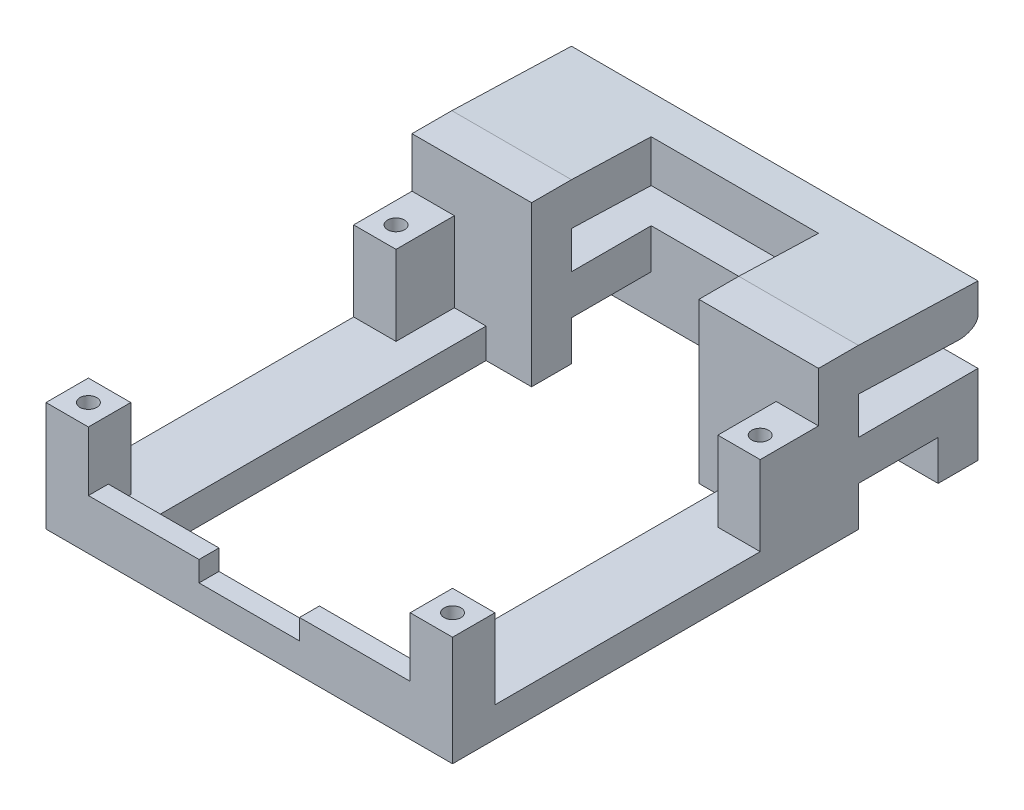
SolidWorks part; units mm, degrees
ref_plane "Front Plane" through (0, 0, 0) normal (0, 0, 1) x (1, 0, 0)
ref_plane "Top Plane" through (0, 0, 0) normal (0, 1, 0) x (1, 0, 0)
ref_plane "Right Plane" through (0, 0, 0) normal (1, 0, 0) x (0, 0, -1)
sketch "Sketch1" plane through (0, 0, 0) normal (0, 1, 0) x (1, 0, 0)
  line L0 (-25.625, 13.905) -> (-25.625, 16.445)
  line L1 (32.375, 41.845) -> (-32.375, 41.845)
  line L2 (32.375, 41.845) -> (32.375, -41.845)
  line L3 (32.375, -41.845) -> (-32.375, -41.845)
  line L4 (-32.375, 41.845) -> (-32.375, -41.845)
  line L5 (32.375, 41.845) -> (-32.375, -41.845) construction
  line L6 (32.375, -41.845) -> (-32.375, 41.845) construction
  line L13 (-32.375, 13.905) -> (-25.625, 13.905)
  line L14 (-32.375, 13.905) -> (-32.375, 7.155)
  line L15 (-32.375, 7.155) -> (-25.625, 7.155)
  line L16 (-25.625, 13.905) -> (-25.625, 7.155)
  line L17 (-32.375, 13.905) -> (-25.625, 7.155) construction
  line L18 (-32.375, 7.155) -> (-25.625, 13.905) construction
  line L19 (25.625, 7.155) -> (32.375, 7.155)
  line L20 (25.625, 7.155) -> (25.625, 13.905)
  line L21 (25.625, 13.905) -> (32.375, 13.905)
  line L22 (32.375, 7.155) -> (32.375, 13.905)
  line L23 (25.625, 7.155) -> (32.375, 13.905) construction
  line L24 (25.625, 13.905) -> (32.375, 7.155) construction
  line L25 (25.625, -35.095) -> (32.375, -35.095)
  line L26 (25.625, -35.095) -> (25.625, -41.845)
  line L27 (25.625, -41.845) -> (32.375, -41.845)
  line L28 (32.375, -35.095) -> (32.375, -41.845)
  line L29 (25.625, -35.095) -> (32.375, -41.845) construction
  line L30 (25.625, -41.845) -> (32.375, -35.095) construction
  line L31 (-25.625, -35.095) -> (-32.375, -35.095)
  line L32 (-25.625, -35.095) -> (-25.625, -41.845)
  line L33 (-25.625, -41.845) -> (-32.375, -41.845)
  line L34 (-32.375, -35.095) -> (-32.375, -41.845)
  line L35 (-25.625, -35.095) -> (-32.375, -41.845) construction
  line L36 (-25.625, -41.845) -> (-32.375, -35.095) construction
  line L47 (-32.375, -41.845) -> (32.375, -41.845)
  line L56 (-25.625, 16.445) -> (-32.375, 16.445)
  line L58 (25.625, 13.905) -> (25.625, 16.445)
  line L59 (25.625, 16.445) -> (32.375, 16.445)
  circle A0 centre (-29, 10.53) radius 1.35
  circle A1 centre (29, 10.53) radius 1.35
  circle A2 centre (-29, -38.47) radius 1.35
  circle A3 centre (29, -38.47) radius 1.35
  point P0 (0, 0)
  point P27 (0, 0)
  dimension "D1" = 2.7
  dimension "D2" = 58
  dimension "D3" = 49
  dimension "D4" = 25.4
  dimension "D5" = 6.75
  dimension "D6" = 2.54
extrude "Boss-Extrude1" add sketch "Sketch1" along normal blind 25.4 contours L31 L32 L3 L26 L25 L2 L19 L20 L21 L1 L4 L13 L16 L15 | L32 L31 L4 L3 A2 | L25 L26 L3 L2 A3 | L21 L20 L19 L2 A1 | L16 L13 L4 L15 A0 | L0 L56 L4 L13 | L59 L58 L21 L2 region at (-29, 0, -15.175) region at (-25.7205, 0, -10.53) region at (0, 0, -0.3894) region at (-29, 0, 35.1905) region at (29, 0, -15.175) region at (32.2795, 0, -10.53) region at (25.7205, 0, 38.47)
sketch "Sketch3" plane through (32.375, 0, 0) normal (1, 0, 0) x (0, 0, -1)
  line L0 (41.845, 18.034) -> (22.795, 18.669)
  line L1 (41.845, 25.4) -> (41.845, 0) construction
  line L2 (22.795, 18.669) -> (22.795, 12.7)
  line L3 (22.795, 12.7) -> (41.845, 12.7)
  line L4 (41.845, 12.7) -> (41.845, 18.034)
  line L5 (41.845, 0) -> (-41.845, 0) construction
  line L6 (41.845, 25.4) -> (22.795, 25.4)
  line L7 (41.845, 25.4) -> (-41.845, 25.4) construction
  line L8 (22.795, 25.4) -> (41.845, 24.765)
  line L9 (41.845, 25.4) -> (41.845, 0) construction
  line L10 (41.845, 24.765) -> (41.845, 25.4)
  point P16 (22.795, 25.4)
  dimension "D1" = 5.969
  dimension "D2" = 5.334
  dimension "D3" = 19.05
  dimension "D4" = 12.7
extrude "Cut-Extrude1" cut sketch "Sketch3" against normal through all
sketch "Sketch5" plane through (32.375, 0, 0) normal (1, 0, 0) x (0, 0, -1)
  line L0 (16.445, 25.4) -> (16.445, 4.7625)
  line L1 (22.795, 25.4) -> (-41.845, 25.4) construction
  line L2 (16.445, 4.7625) -> (-41.845, 4.7625)
  line L3 (-41.845, 4.7625) -> (-41.845, 25.4)
  line L4 (-41.845, 25.4) -> (16.445, 25.4)
  line L6 (41.845, 0) -> (-41.845, 0) construction
  dimension "D2" = 4.7625
extrude "Cut-Extrude3" cut sketch "Sketch5" against normal through all
extrude "Boss-Extrude2" add sketch "Sketch1<3>" along normal blind 12.7 from surface contours L25 L26 L3 L2 A3 | L32 L31 L4 L3 A2 | L16 L13 L4 L15 A0 | L21 L20 L19 L2 A1 | L0 L56 L4 L13 | L59 L58 L21 L2 region at (-29, 0, -15.175) region at (-25.7205, 0, -10.53) region at (-29, 0, 35.1905) region at (29, 0, -15.175) region at (32.2795, 0, -10.53) region at (25.7205, 0, 38.47) starting at face at (-29, 4.7625, 37.12)
sketch "Sketch1<3>" plane through (0, 0, 0) normal (0, 1, 0) x (1, 0, 0) same geometry as "Sketch1"
sketch "Sketch25" plane through (0, 17.4625, 0) normal (0, 1, 0) x (1, 0, 0)
  line L1 (-32.5, -41.97) -> (52.5, -41.97) construction
  line L2 (-32.5, -41.97) -> (-32.5, 14.03) construction
  line L3 (-32.5, 14.03) -> (52.5, 14.03) construction
  line L4 (52.5, -41.97) -> (52.5, 14.03) construction
  circle A0 centre (-29, -38.47) radius 1.375
  circle A1 centre (-29, 10.53) radius 1.375
  circle A2 centre (29, -38.47) radius 1.375
  circle A3 centre (29, 10.53) radius 1.375
  point P12 (0, 0)
  point P13 (0, 0)
  point P14 (0, 0)
  point P15 (0, 0)
  point P16 (0, 0)
  point P17 (-25.2609, 1.5382)
  point P18 (25.625, -30.2592)
  point P19 (29, -38.7875)
  dimension "D5" = 2.75
  dimension "D1" = 56
  dimension "D2" = 85
  dimension "D3" = 49
  dimension "D4" = 58
  dimension "D6" = 3.5
  dimension "D7" = 3.5
sketch "Sketch7" plane through (0, 12.7, 0) normal (0, 1, 0) x (1, 0, 0)
  line L0 (-25.625, -41.845) -> (25.625, -41.845) construction
  line L1 (-13.325, -38.67) -> (13.325, -38.67)
  line L2 (-13.325, -38.67) -> (-13.325, 35.495)
  line L3 (-13.325, 35.495) -> (13.325, 35.495)
  line L4 (13.325, -38.67) -> (13.325, 35.495)
  line L7 (32.375, -35.095) -> (32.375, 7.155) construction
  line L8 (32.375, 41.845) -> (-32.375, 41.845) construction
  line L12 (-25.625, 16.445) -> (25.625, 16.445) construction
  line L13 (-13.325, -38.67) -> (-20.574, -38.67)
  line L14 (-13.325, -38.67) -> (-13.325, 16.445)
  line L15 (-13.325, 16.445) -> (-20.574, 16.445)
  line L16 (-20.574, -38.67) -> (-20.574, 16.445)
  line L17 (-32.375, 16.445) -> (32.375, 16.445) construction
  line L18 (13.325, -38.67) -> (20.574, -38.67)
  line L19 (13.325, -38.67) -> (13.325, 16.445)
  line L20 (13.325, 16.445) -> (20.574, 16.445)
  line L21 (20.574, -38.67) -> (20.574, 16.445)
  point P8 (0, -38.67)
  line M8 (-32.375, 22.795) -> (32.375, 22.795)
  dimension "D1" = 19.05
  dimension "D2" = 6.35
  dimension "D3" = 3.175
  dimension "D4" = 41.148
extrude "Cut-Extrude6" cut sketch "Sketch7" against normal through all both and the other way through all contours L1 L4 L2 M8 | L4 L3 L2 M8 | L16 L13 L2 L15 | L18 L21 L20 L4 region at (0, 12.7, 7.9375) region at (-16.9495, 12.7, 11.1125) region at (16.9495, 12.7, 11.1125) region at (0, 12.7, -29.145)
sketch "Sketch26" plane through (32.375, 0, 0) normal (1, 0, 0) x (0, 0, -1)
  line L0 (41.845, 0) -> (-41.845, 0) construction
  line L1 (22.795, 0) -> (35.495, 0)
  line L2 (22.795, 0) -> (22.795, 6.35)
  line L3 (22.795, 6.35) -> (35.495, 6.35)
  line L4 (35.495, 0) -> (35.495, 6.35)
  line L5 (22.795, 12.7) -> (41.845, 12.7) construction
  point P10 (0, 0)
  dimension "D1" = 6.35
  dimension "D2" = 6.35
extrude "Cut-Extrude17" cut sketch "Sketch26" against normal through all
fillet "Fillet1" radius 1.905 1 edges at (0, 18.034, -41.845) second distance 3.175 first distance on face at (0, 21.3995, -41.845)
sketch "Sketch22" plane through (0, 0, 41.845) normal (0, 0, 1) x (1, 0, 0)
  line L0 (-25.625, 4.7625) -> (25.625, 4.7625) construction
  line L1 (-25.625, 4.7625) -> (-8, 4.7625)
  line L2 (-25.625, 4.7625) -> (-25.625, 8)
  line L3 (-25.625, 8) -> (-8, 8)
  line L4 (-8, 4.7625) -> (-8, 8)
  line L5 (25.625, 4.7625) -> (8, 4.7625)
  line L6 (25.625, 4.7625) -> (25.625, 8)
  line L7 (25.625, 8) -> (8, 8)
  line L8 (8, 4.7625) -> (8, 8)
  line L9 (32.375, 0) -> (-32.375, 0) construction
  dimension "D1" = 16
  dimension "D2" = 8
extrude "Boss-Extrude6" add sketch "Sketch22" against normal blind 3.175
